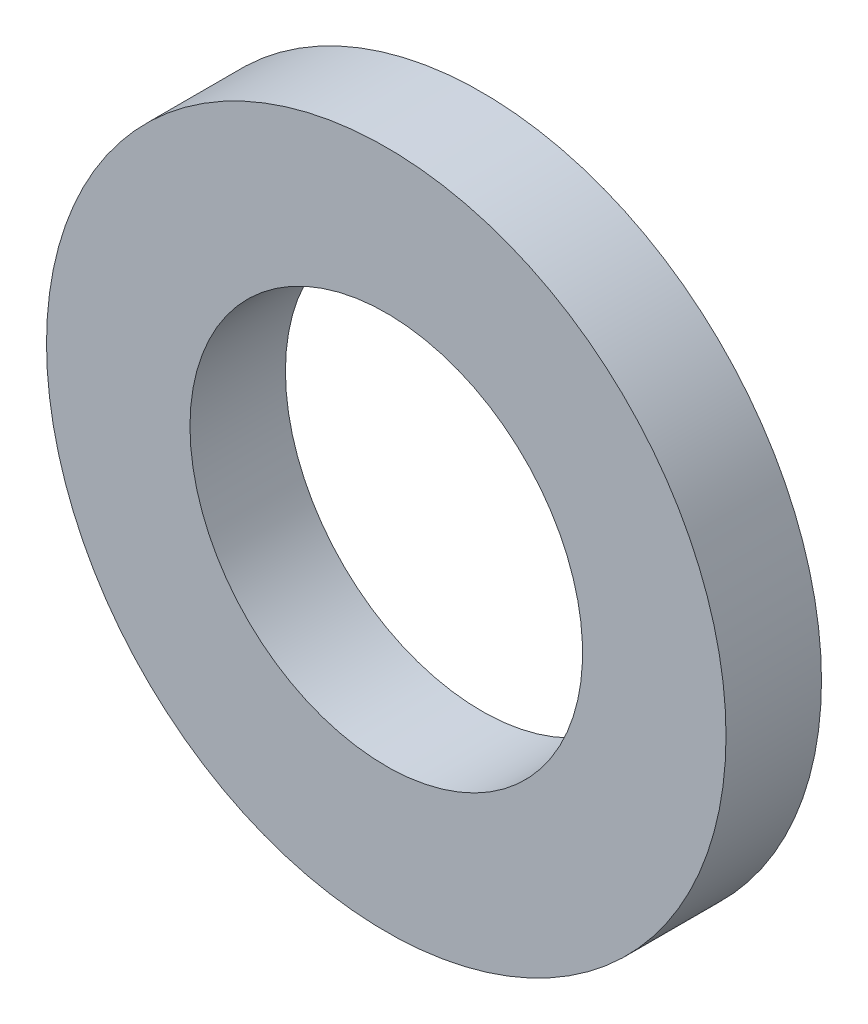
SolidWorks part; units mm, degrees
ref_plane "Front Plane" through (0, 0, 0) normal (0, 0, 1) x (1, 0, 0)
ref_plane "Top Plane" through (0, 0, 0) normal (0, 1, 0) x (1, 0, 0)
ref_plane "Right Plane" through (0, 0, 0) normal (1, 0, 0) x (0, 0, -1)
sketch "Sketch1" plane through (0, 0, 0) normal (0, 0, 1) x (1, 0, 0)
  circle A0 centre (0, 0) radius 17.145
  circle A1 centre (0, 0) radius 9.906
  dimension "D1" = 34.29
  dimension "D2" = 19.812
extrude "Boss-Extrude1" add sketch "Sketch1" along normal blind 4.8169
equation "\"D1@Boss-Extrude1\"=\"WasherThickness@BladeStackupWithSprocket.Assembly\""
